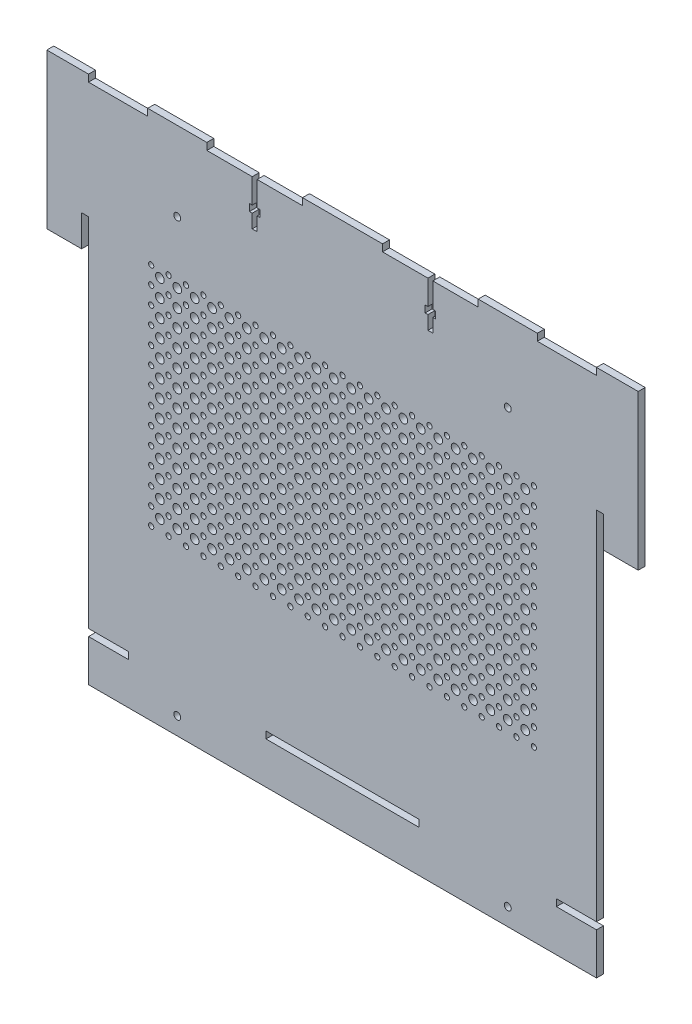
SolidWorks part; units mm, degrees
ref_plane "Front" through (0, 0, 0) normal (0, 0, 1) x (1, 0, 0)
ref_plane "Top" through (0, 0, 0) normal (0, 1, 0) x (1, 0, 0)
ref_plane "Right" through (0, 0, 0) normal (1, 0, 0) x (0, 0, -1)
sketch "Sketch1" plane through (0, 0, 0) normal (0, 0, 1) x (1, 0, 0)
  line L0 (-146, 106.5) -> (146, 106.5) construction
  line L1 (146, -152) -> (-146, -152)
  line L2 (146, -152) -> (146, -128)
  line L3 (146, 152) -> (-146, 152) construction
  line L4 (-146, -152) -> (-146, -128)
  line L5 (146, -152) -> (-146, 152) construction
  line L6 (146, 152) -> (-146, -152) construction
  line L7 (-146, 148) -> (-112, 148)
  line L8 (-112, 148) -> (-112, 152)
  line L9 (-112, 152) -> (-78, 152)
  line L10 (-78, 152) -> (-78, 148)
  line L11 (-78, 148) -> (-51.9, 148)
  line L12 (-23, 148) -> (-23, 152)
  line L13 (-23, 152) -> (23, 152)
  line L14 (23, 152) -> (23, 148)
  line L15 (23, 148) -> (49.1, 148)
  line L16 (78, 148) -> (78, 152)
  line L17 (78, 152) -> (112, 152)
  line L18 (112, 152) -> (112, 148)
  line L19 (112, 148) -> (146, 148)
  line L20 (-146, -142) -> (146, -142) construction
  line L21 (-95, 152) -> (-95, 106.5) construction
  line L22 (95, 152) -> (95, 106.5) construction
  line L23 (0, 106.5) -> (0, -142) construction
  line L24 (-146, 152) -> (-170, 152)
  line L25 (116.5, 80) -> (-116.5, 80) construction
  line L26 (116.5, 80) -> (116.5, -64) construction
  line L27 (116.5, -64) -> (-116.5, -64) construction
  line L28 (-116.5, 80) -> (-116.5, -64) construction
  line L29 (116.5, 80) -> (-116.5, -64) construction
  line L30 (116.5, -64) -> (-116.5, 80) construction
  line L31 (-170, 152) -> (-170, 63)
  line L32 (-170, 63) -> (-150, 63)
  line L33 (-150, 63) -> (-150, 81)
  line L34 (-150, 81) -> (-146, 81)
  line L35 (150, 81) -> (146, 81)
  line L36 (150, 63) -> (150, 81)
  line L37 (170, 63) -> (150, 63)
  line L38 (170, 152) -> (170, 63)
  line L39 (146, 152) -> (170, 152)
  line L40 (146, 148) -> (146, 152)
  line L41 (-146, 148) -> (-146, 152)
  line L42 (-50.5, 148) -> (-50.5, 122) construction
  line L43 (50.5, 148) -> (50.5, 122) construction
  line L44 (-51.9, 148) -> (-51.9, 133.8447)
  line L45 (49.1, 148) -> (49.1, 122)
  line L46 (-49.1, 148) -> (-49.1, 133.8447)
  line L47 (51.9, 148) -> (51.9, 122)
  line L48 (146, 122) -> (-146, 122) construction
  line L49 (-51.9, 122) -> (-49.1, 122)
  line L50 (-50.5, 148) -> (-50.5, 119.0546) construction
  line L51 (-51.9, 148) -> (-51.9, 119.0546) construction
  line L52 (49.1, 122) -> (51.9, 122)
  line L53 (50.5, 148) -> (50.5, 119.0546) construction
  line L54 (49.1, 148) -> (49.1, 119.0546) construction
  line L55 (-49.1, 148) -> (-23, 148)
  line L56 (51.9, 148) -> (78, 148)
  line L57 (-53.5, 133.8447) -> (-53.5, 129.8447)
  line L58 (-53.5, 133.8447) -> (-51.9, 133.8447)
  line L59 (-53.5, 129.8447) -> (-51.9, 129.8447)
  line L60 (-51.9, 129.8447) -> (-51.9, 122)
  line L61 (-47.5, 129.8447) -> (-49.1, 129.8447)
  line L62 (-47.5, 133.8447) -> (-47.5, 129.8447)
  line L63 (-47.5, 133.8447) -> (-49.1, 133.8447)
  line L64 (-49.1, 129.8447) -> (-49.1, 122)
  line L65 (-211.8235, -128) -> (236.7323, -128) construction
  line L66 (-146, -128) -> (-122.9474, -128)
  line L67 (-122.9474, -128) -> (-122.9474, -124)
  line L68 (-122.9474, -124) -> (-146, -124)
  line L69 (122.9474, -128) -> (146, -128)
  line L70 (122.9474, -128) -> (122.9474, -124)
  line L71 (122.9474, -124) -> (146, -124)
  line L72 (-44, -128) -> (-44, -124)
  line L73 (-44, -124) -> (44, -124)
  line L74 (44, -124) -> (44, -128)
  line L75 (-146, -124) -> (-146, 106.5)
  line L76 (146, -124) -> (146, 106.5)
  line L77 (-44, -128) -> (44, -128)
  line L78 (47.5, 133.8447) -> (49.1, 133.8447)
  line L79 (47.5, 133.8447) -> (47.5, 129.8447)
  line L80 (47.5, 129.8447) -> (49.1, 129.8447)
  line L81 (53.5, 129.8447) -> (51.9, 129.8447)
  line L82 (53.5, 133.8447) -> (51.9, 133.8447)
  line L83 (53.5, 133.8447) -> (53.5, 129.8447)
  circle A0 centre (-95, 106.5) radius 2
  circle A1 centre (95, 106.5) radius 2
  circle A2 centre (-95, -142) radius 2
  circle A3 centre (95, -142) radius 2
  circle A4 centre (-110, 75) radius 1.5
  circle A5 centre (-100, 75) radius 1.5
  circle A6 centre (-90, 75) radius 1.5
  circle A7 centre (-80, 75) radius 1.5
  circle A8 centre (-70, 75) radius 1.5
  circle A9 centre (-60, 75) radius 1.5
  circle A10 centre (-50, 75) radius 1.5
  circle A11 centre (-40, 75) radius 1.5
  circle A12 centre (-30, 75) radius 1.5
  circle A13 centre (-20, 75) radius 1.5
  circle A14 centre (-10, 75) radius 1.5
  circle A15 centre (0, 75) radius 1.5
  circle A16 centre (10, 75) radius 1.5
  circle A17 centre (20, 75) radius 1.5
  circle A18 centre (30, 75) radius 1.5
  circle A19 centre (40, 75) radius 1.5
  circle A20 centre (50, 75) radius 1.5
  circle A21 centre (60, 75) radius 1.5
  circle A22 centre (70, 75) radius 1.5
  circle A23 centre (80, 75) radius 1.5
  circle A24 centre (90, 75) radius 1.5
  circle A25 centre (100, 75) radius 1.5
  circle A26 centre (110, 75) radius 1.5
  circle A27 centre (-100, 65) radius 1.5
  circle A28 centre (-90, 65) radius 1.5
  circle A29 centre (-80, 65) radius 1.5
  circle A30 centre (-70, 65) radius 1.5
  circle A31 centre (-60, 65) radius 1.5
  circle A32 centre (-50, 65) radius 1.5
  circle A33 centre (-40, 65) radius 1.5
  circle A34 centre (-30, 65) radius 1.5
  circle A35 centre (-20, 65) radius 1.5
  circle A36 centre (-10, 65) radius 1.5
  circle A37 centre (0, 65) radius 1.5
  circle A38 centre (10, 65) radius 1.5
  circle A39 centre (20, 65) radius 1.5
  circle A40 centre (30, 65) radius 1.5
  circle A41 centre (40, 65) radius 1.5
  circle A42 centre (50, 65) radius 1.5
  circle A43 centre (60, 65) radius 1.5
  circle A44 centre (70, 65) radius 1.5
  circle A45 centre (80, 65) radius 1.5
  circle A46 centre (90, 65) radius 1.5
  circle A47 centre (100, 65) radius 1.5
  circle A48 centre (110, 65) radius 1.5
  circle A49 centre (-100, 55) radius 1.5
  circle A50 centre (-90, 55) radius 1.5
  circle A51 centre (-80, 55) radius 1.5
  circle A52 centre (-70, 55) radius 1.5
  circle A53 centre (-60, 55) radius 1.5
  circle A54 centre (-50, 55) radius 1.5
  circle A55 centre (-40, 55) radius 1.5
  circle A56 centre (-30, 55) radius 1.5
  circle A57 centre (-20, 55) radius 1.5
  circle A58 centre (-10, 55) radius 1.5
  circle A59 centre (0, 55) radius 1.5
  circle A60 centre (10, 55) radius 1.5
  circle A61 centre (20, 55) radius 1.5
  circle A62 centre (30, 55) radius 1.5
  circle A63 centre (40, 55) radius 1.5
  circle A64 centre (50, 55) radius 1.5
  circle A65 centre (60, 55) radius 1.5
  circle A66 centre (70, 55) radius 1.5
  circle A67 centre (80, 55) radius 1.5
  circle A68 centre (90, 55) radius 1.5
  circle A69 centre (100, 55) radius 1.5
  circle A70 centre (110, 55) radius 1.5
  circle A71 centre (-100, 45) radius 1.5
  circle A72 centre (-90, 45) radius 1.5
  circle A73 centre (-80, 45) radius 1.5
  circle A74 centre (-70, 45) radius 1.5
  circle A75 centre (-60, 45) radius 1.5
  circle A76 centre (-50, 45) radius 1.5
  circle A77 centre (-40, 45) radius 1.5
  circle A78 centre (-30, 45) radius 1.5
  circle A79 centre (-20, 45) radius 1.5
  circle A80 centre (-10, 45) radius 1.5
  circle A81 centre (0, 45) radius 1.5
  circle A82 centre (10, 45) radius 1.5
  circle A83 centre (20, 45) radius 1.5
  circle A84 centre (30, 45) radius 1.5
  circle A85 centre (40, 45) radius 1.5
  circle A86 centre (50, 45) radius 1.5
  circle A87 centre (60, 45) radius 1.5
  circle A88 centre (70, 45) radius 1.5
  circle A89 centre (80, 45) radius 1.5
  circle A90 centre (90, 45) radius 1.5
  circle A91 centre (100, 45) radius 1.5
  circle A92 centre (110, 45) radius 1.5
  circle A93 centre (-100, 35) radius 1.5
  circle A94 centre (-90, 35) radius 1.5
  circle A95 centre (-80, 35) radius 1.5
  circle A96 centre (-70, 35) radius 1.5
  circle A97 centre (-60, 35) radius 1.5
  circle A98 centre (-50, 35) radius 1.5
  circle A99 centre (-40, 35) radius 1.5
  circle A100 centre (-30, 35) radius 1.5
  circle A101 centre (-20, 35) radius 1.5
  circle A102 centre (-10, 35) radius 1.5
  circle A103 centre (0, 35) radius 1.5
  circle A104 centre (10, 35) radius 1.5
  circle A105 centre (20, 35) radius 1.5
  circle A106 centre (30, 35) radius 1.5
  circle A107 centre (40, 35) radius 1.5
  circle A108 centre (50, 35) radius 1.5
  circle A109 centre (60, 35) radius 1.5
  circle A110 centre (70, 35) radius 1.5
  circle A111 centre (80, 35) radius 1.5
  circle A112 centre (90, 35) radius 1.5
  circle A113 centre (100, 35) radius 1.5
  circle A114 centre (110, 35) radius 1.5
  circle A115 centre (-100, 25) radius 1.5
  circle A116 centre (-90, 25) radius 1.5
  circle A117 centre (-80, 25) radius 1.5
  circle A118 centre (-70, 25) radius 1.5
  circle A119 centre (-60, 25) radius 1.5
  circle A120 centre (-50, 25) radius 1.5
  circle A121 centre (-40, 25) radius 1.5
  circle A122 centre (-30, 25) radius 1.5
  circle A123 centre (-20, 25) radius 1.5
  circle A124 centre (-10, 25) radius 1.5
  circle A125 centre (0, 25) radius 1.5
  circle A126 centre (10, 25) radius 1.5
  circle A127 centre (20, 25) radius 1.5
  circle A128 centre (30, 25) radius 1.5
  circle A129 centre (40, 25) radius 1.5
  circle A130 centre (50, 25) radius 1.5
  circle A131 centre (60, 25) radius 1.5
  circle A132 centre (70, 25) radius 1.5
  circle A133 centre (80, 25) radius 1.5
  circle A134 centre (90, 25) radius 1.5
  circle A135 centre (100, 25) radius 1.5
  circle A136 centre (110, 25) radius 1.5
  circle A137 centre (-100, 15) radius 1.5
  circle A138 centre (-90, 15) radius 1.5
  circle A139 centre (-80, 15) radius 1.5
  circle A140 centre (-70, 15) radius 1.5
  circle A141 centre (-60, 15) radius 1.5
  circle A142 centre (-50, 15) radius 1.5
  circle A143 centre (-40, 15) radius 1.5
  circle A144 centre (-30, 15) radius 1.5
  circle A145 centre (-20, 15) radius 1.5
  circle A146 centre (-10, 15) radius 1.5
  circle A147 centre (0, 15) radius 1.5
  circle A148 centre (10, 15) radius 1.5
  circle A149 centre (20, 15) radius 1.5
  circle A150 centre (30, 15) radius 1.5
  circle A151 centre (40, 15) radius 1.5
  circle A152 centre (50, 15) radius 1.5
  circle A153 centre (60, 15) radius 1.5
  circle A154 centre (70, 15) radius 1.5
  circle A155 centre (80, 15) radius 1.5
  circle A156 centre (90, 15) radius 1.5
  circle A157 centre (100, 15) radius 1.5
  circle A158 centre (110, 15) radius 1.5
  circle A159 centre (-100, 5) radius 1.5
  circle A160 centre (-90, 5) radius 1.5
  circle A161 centre (-80, 5) radius 1.5
  circle A162 centre (-70, 5) radius 1.5
  circle A163 centre (-60, 5) radius 1.5
  circle A164 centre (-50, 5) radius 1.5
  circle A165 centre (-40, 5) radius 1.5
  circle A166 centre (-30, 5) radius 1.5
  circle A167 centre (-20, 5) radius 1.5
  circle A168 centre (-10, 5) radius 1.5
  circle A169 centre (0, 5) radius 1.5
  circle A170 centre (10, 5) radius 1.5
  circle A171 centre (20, 5) radius 1.5
  circle A172 centre (30, 5) radius 1.5
  circle A173 centre (40, 5) radius 1.5
  circle A174 centre (50, 5) radius 1.5
  circle A175 centre (60, 5) radius 1.5
  circle A176 centre (70, 5) radius 1.5
  circle A177 centre (80, 5) radius 1.5
  circle A178 centre (90, 5) radius 1.5
  circle A179 centre (100, 5) radius 1.5
  circle A180 centre (110, 5) radius 1.5
  circle A181 centre (-100, -5) radius 1.5
  circle A182 centre (-90, -5) radius 1.5
  circle A183 centre (-80, -5) radius 1.5
  circle A184 centre (-70, -5) radius 1.5
  circle A185 centre (-60, -5) radius 1.5
  circle A186 centre (-50, -5) radius 1.5
  circle A187 centre (-40, -5) radius 1.5
  circle A188 centre (-30, -5) radius 1.5
  circle A189 centre (-20, -5) radius 1.5
  circle A190 centre (-10, -5) radius 1.5
  circle A191 centre (0, -5) radius 1.5
  circle A192 centre (10, -5) radius 1.5
  circle A193 centre (20, -5) radius 1.5
  circle A194 centre (30, -5) radius 1.5
  circle A195 centre (40, -5) radius 1.5
  circle A196 centre (50, -5) radius 1.5
  circle A197 centre (60, -5) radius 1.5
  circle A198 centre (70, -5) radius 1.5
  circle A199 centre (80, -5) radius 1.5
  circle A200 centre (90, -5) radius 1.5
  circle A201 centre (100, -5) radius 1.5
  circle A202 centre (110, -5) radius 1.5
  circle A203 centre (-100, -15) radius 1.5
  circle A204 centre (-90, -15) radius 1.5
  circle A205 centre (-80, -15) radius 1.5
  circle A206 centre (-70, -15) radius 1.5
  circle A207 centre (-60, -15) radius 1.5
  circle A208 centre (-50, -15) radius 1.5
  circle A209 centre (-40, -15) radius 1.5
  circle A210 centre (-30, -15) radius 1.5
  circle A211 centre (-20, -15) radius 1.5
  circle A212 centre (-10, -15) radius 1.5
  circle A213 centre (0, -15) radius 1.5
  circle A214 centre (10, -15) radius 1.5
  circle A215 centre (20, -15) radius 1.5
  circle A216 centre (30, -15) radius 1.5
  circle A217 centre (40, -15) radius 1.5
  circle A218 centre (50, -15) radius 1.5
  circle A219 centre (60, -15) radius 1.5
  circle A220 centre (70, -15) radius 1.5
  circle A221 centre (80, -15) radius 1.5
  circle A222 centre (90, -15) radius 1.5
  circle A223 centre (100, -15) radius 1.5
  circle A224 centre (110, -15) radius 1.5
  circle A225 centre (-100, -25) radius 1.5
  circle A226 centre (-90, -25) radius 1.5
  circle A227 centre (-80, -25) radius 1.5
  circle A228 centre (-70, -25) radius 1.5
  circle A229 centre (-60, -25) radius 1.5
  circle A230 centre (-50, -25) radius 1.5
  circle A231 centre (-40, -25) radius 1.5
  circle A232 centre (-30, -25) radius 1.5
  circle A233 centre (-20, -25) radius 1.5
  circle A234 centre (-10, -25) radius 1.5
  circle A235 centre (0, -25) radius 1.5
  circle A236 centre (10, -25) radius 1.5
  circle A237 centre (20, -25) radius 1.5
  circle A238 centre (30, -25) radius 1.5
  circle A239 centre (40, -25) radius 1.5
  circle A240 centre (50, -25) radius 1.5
  circle A241 centre (60, -25) radius 1.5
  circle A242 centre (70, -25) radius 1.5
  circle A243 centre (80, -25) radius 1.5
  circle A244 centre (90, -25) radius 1.5
  circle A245 centre (100, -25) radius 1.5
  circle A246 centre (110, -25) radius 1.5
  circle A247 centre (-100, -35) radius 1.5
  circle A248 centre (-90, -35) radius 1.5
  circle A249 centre (-80, -35) radius 1.5
  circle A250 centre (-70, -35) radius 1.5
  circle A251 centre (-60, -35) radius 1.5
  circle A252 centre (-50, -35) radius 1.5
  circle A253 centre (-40, -35) radius 1.5
  circle A254 centre (-30, -35) radius 1.5
  circle A255 centre (-20, -35) radius 1.5
  circle A256 centre (-10, -35) radius 1.5
  circle A257 centre (0, -35) radius 1.5
  circle A258 centre (10, -35) radius 1.5
  circle A259 centre (20, -35) radius 1.5
  circle A260 centre (30, -35) radius 1.5
  circle A261 centre (40, -35) radius 1.5
  circle A262 centre (50, -35) radius 1.5
  circle A263 centre (60, -35) radius 1.5
  circle A264 centre (70, -35) radius 1.5
  circle A265 centre (80, -35) radius 1.5
  circle A266 centre (90, -35) radius 1.5
  circle A267 centre (100, -35) radius 1.5
  circle A268 centre (110, -35) radius 1.5
  circle A269 centre (-100, -45) radius 1.5
  circle A270 centre (-90, -45) radius 1.5
  circle A271 centre (-80, -45) radius 1.5
  circle A272 centre (-70, -45) radius 1.5
  circle A273 centre (-60, -45) radius 1.5
  circle A274 centre (-50, -45) radius 1.5
  circle A275 centre (-40, -45) radius 1.5
  circle A276 centre (-30, -45) radius 1.5
  circle A277 centre (-20, -45) radius 1.5
  circle A278 centre (-10, -45) radius 1.5
  circle A279 centre (0, -45) radius 1.5
  circle A280 centre (10, -45) radius 1.5
  circle A281 centre (20, -45) radius 1.5
  circle A282 centre (30, -45) radius 1.5
  circle A283 centre (40, -45) radius 1.5
  circle A284 centre (50, -45) radius 1.5
  circle A285 centre (60, -45) radius 1.5
  circle A286 centre (70, -45) radius 1.5
  circle A287 centre (80, -45) radius 1.5
  circle A288 centre (90, -45) radius 1.5
  circle A289 centre (100, -45) radius 1.5
  circle A290 centre (110, -45) radius 1.5
  circle A291 centre (-100, -55) radius 1.5
  circle A292 centre (-90, -55) radius 1.5
  circle A293 centre (-80, -55) radius 1.5
  circle A294 centre (-70, -55) radius 1.5
  circle A295 centre (-60, -55) radius 1.5
  circle A296 centre (-50, -55) radius 1.5
  circle A297 centre (-40, -55) radius 1.5
  circle A298 centre (-30, -55) radius 1.5
  circle A299 centre (-20, -55) radius 1.5
  circle A300 centre (-10, -55) radius 1.5
  circle A301 centre (0, -55) radius 1.5
  circle A302 centre (10, -55) radius 1.5
  circle A303 centre (20, -55) radius 1.5
  circle A304 centre (30, -55) radius 1.5
  circle A305 centre (40, -55) radius 1.5
  circle A306 centre (50, -55) radius 1.5
  circle A307 centre (60, -55) radius 1.5
  circle A308 centre (70, -55) radius 1.5
  circle A309 centre (80, -55) radius 1.5
  circle A310 centre (90, -55) radius 1.5
  circle A311 centre (100, -55) radius 1.5
  circle A312 centre (110, -55) radius 1.5
  circle A313 centre (-110, 65) radius 1.5
  circle A314 centre (-110, 55) radius 1.5
  circle A315 centre (-110, 45) radius 1.5
  circle A316 centre (-110, 35) radius 1.5
  circle A317 centre (-110, 25) radius 1.5
  circle A318 centre (-110, 15) radius 1.5
  circle A319 centre (-110, 5) radius 1.5
  circle A320 centre (-110, -5) radius 1.5
  circle A321 centre (-110, -15) radius 1.5
  circle A322 centre (-110, -25) radius 1.5
  circle A323 centre (-110, -35) radius 1.5
  circle A324 centre (-110, -45) radius 1.5
  circle A325 centre (-110, -55) radius 1.5
  circle A326 centre (-95, 71) radius 2.5
  circle A327 centre (-85, 71) radius 2.5
  circle A328 centre (-75, 71) radius 2.5
  circle A329 centre (-65, 71) radius 2.5
  circle A330 centre (-55, 71) radius 2.5
  circle A331 centre (-45, 71) radius 2.5
  circle A332 centre (-35, 71) radius 2.5
  circle A333 centre (-25, 71) radius 2.5
  circle A334 centre (-15, 71) radius 2.5
  circle A335 centre (-5, 71) radius 2.5
  circle A336 centre (5, 71) radius 2.5
  circle A337 centre (15, 71) radius 2.5
  circle A338 centre (25, 71) radius 2.5
  circle A339 centre (35, 71) radius 2.5
  circle A340 centre (45, 71) radius 2.5
  circle A341 centre (55, 71) radius 2.5
  circle A342 centre (65, 71) radius 2.5
  circle A343 centre (75, 71) radius 2.5
  circle A344 centre (85, 71) radius 2.5
  circle A345 centre (95, 71) radius 2.5
  circle A346 centre (105, 71) radius 2.5
  circle A347 centre (-95, 61) radius 2.5
  circle A348 centre (-85, 61) radius 2.5
  circle A349 centre (-75, 61) radius 2.5
  circle A350 centre (-65, 61) radius 2.5
  circle A351 centre (-55, 61) radius 2.5
  circle A352 centre (-45, 61) radius 2.5
  circle A353 centre (-35, 61) radius 2.5
  circle A354 centre (-25, 61) radius 2.5
  circle A355 centre (-15, 61) radius 2.5
  circle A356 centre (-5, 61) radius 2.5
  circle A357 centre (5, 61) radius 2.5
  circle A358 centre (15, 61) radius 2.5
  circle A359 centre (25, 61) radius 2.5
  circle A360 centre (35, 61) radius 2.5
  circle A361 centre (45, 61) radius 2.5
  circle A362 centre (55, 61) radius 2.5
  circle A363 centre (65, 61) radius 2.5
  circle A364 centre (75, 61) radius 2.5
  circle A365 centre (85, 61) radius 2.5
  circle A366 centre (95, 61) radius 2.5
  circle A367 centre (105, 61) radius 2.5
  circle A368 centre (-95, 51) radius 2.5
  circle A369 centre (-85, 51) radius 2.5
  circle A370 centre (-75, 51) radius 2.5
  circle A371 centre (-65, 51) radius 2.5
  circle A372 centre (-55, 51) radius 2.5
  circle A373 centre (-45, 51) radius 2.5
  circle A374 centre (-35, 51) radius 2.5
  circle A375 centre (-25, 51) radius 2.5
  circle A376 centre (-15, 51) radius 2.5
  circle A377 centre (-5, 51) radius 2.5
  circle A378 centre (5, 51) radius 2.5
  circle A379 centre (15, 51) radius 2.5
  circle A380 centre (25, 51) radius 2.5
  circle A381 centre (35, 51) radius 2.5
  circle A382 centre (45, 51) radius 2.5
  circle A383 centre (55, 51) radius 2.5
  circle A384 centre (65, 51) radius 2.5
  circle A385 centre (75, 51) radius 2.5
  circle A386 centre (85, 51) radius 2.5
  circle A387 centre (95, 51) radius 2.5
  circle A388 centre (105, 51) radius 2.5
  circle A389 centre (-95, 41) radius 2.5
  circle A390 centre (-85, 41) radius 2.5
  circle A391 centre (-75, 41) radius 2.5
  circle A392 centre (-65, 41) radius 2.5
  circle A393 centre (-55, 41) radius 2.5
  circle A394 centre (-45, 41) radius 2.5
  circle A395 centre (-35, 41) radius 2.5
  circle A396 centre (-25, 41) radius 2.5
  circle A397 centre (-15, 41) radius 2.5
  circle A398 centre (-5, 41) radius 2.5
  circle A399 centre (5, 41) radius 2.5
  circle A400 centre (15, 41) radius 2.5
  circle A401 centre (25, 41) radius 2.5
  circle A402 centre (35, 41) radius 2.5
  circle A403 centre (45, 41) radius 2.5
  circle A404 centre (55, 41) radius 2.5
  circle A405 centre (65, 41) radius 2.5
  circle A406 centre (75, 41) radius 2.5
  circle A407 centre (85, 41) radius 2.5
  circle A408 centre (95, 41) radius 2.5
  circle A409 centre (105, 41) radius 2.5
  circle A410 centre (-95, 31) radius 2.5
  circle A411 centre (-85, 31) radius 2.5
  circle A412 centre (-75, 31) radius 2.5
  circle A413 centre (-65, 31) radius 2.5
  circle A414 centre (-55, 31) radius 2.5
  circle A415 centre (-45, 31) radius 2.5
  circle A416 centre (-35, 31) radius 2.5
  circle A417 centre (-25, 31) radius 2.5
  circle A418 centre (-105, 71) radius 2.5
  circle A419 centre (-15, 31) radius 2.5
  circle A420 centre (-5, 31) radius 2.5
  circle A421 centre (5, 31) radius 2.5
  circle A422 centre (15, 31) radius 2.5
  circle A423 centre (25, 31) radius 2.5
  circle A424 centre (35, 31) radius 2.5
  circle A425 centre (45, 31) radius 2.5
  circle A426 centre (55, 31) radius 2.5
  circle A427 centre (65, 31) radius 2.5
  circle A428 centre (75, 31) radius 2.5
  circle A429 centre (85, 31) radius 2.5
  circle A430 centre (95, 31) radius 2.5
  circle A431 centre (105, 31) radius 2.5
  circle A432 centre (-95, 21) radius 2.5
  circle A433 centre (-85, 21) radius 2.5
  circle A434 centre (-75, 21) radius 2.5
  circle A435 centre (-65, 21) radius 2.5
  circle A436 centre (-55, 21) radius 2.5
  circle A437 centre (-45, 21) radius 2.5
  circle A438 centre (-35, 21) radius 2.5
  circle A439 centre (-25, 21) radius 2.5
  circle A440 centre (-15, 21) radius 2.5
  circle A441 centre (-5, 21) radius 2.5
  circle A442 centre (5, 21) radius 2.5
  circle A443 centre (15, 21) radius 2.5
  circle A444 centre (25, 21) radius 2.5
  circle A445 centre (35, 21) radius 2.5
  circle A446 centre (45, 21) radius 2.5
  circle A447 centre (55, 21) radius 2.5
  circle A448 centre (65, 21) radius 2.5
  circle A449 centre (75, 21) radius 2.5
  circle A450 centre (85, 21) radius 2.5
  circle A451 centre (95, 21) radius 2.5
  circle A452 centre (105, 21) radius 2.5
  circle A453 centre (-95, 11) radius 2.5
  circle A454 centre (-85, 11) radius 2.5
  circle A455 centre (-75, 11) radius 2.5
  circle A456 centre (-65, 11) radius 2.5
  circle A457 centre (-55, 11) radius 2.5
  circle A458 centre (-45, 11) radius 2.5
  circle A459 centre (-35, 11) radius 2.5
  circle A460 centre (-25, 11) radius 2.5
  circle A461 centre (-15, 11) radius 2.5
  circle A462 centre (-5, 11) radius 2.5
  circle A463 centre (5, 11) radius 2.5
  circle A464 centre (15, 11) radius 2.5
  circle A465 centre (25, 11) radius 2.5
  circle A466 centre (35, 11) radius 2.5
  circle A467 centre (45, 11) radius 2.5
  circle A468 centre (55, 11) radius 2.5
  circle A469 centre (65, 11) radius 2.5
  circle A470 centre (75, 11) radius 2.5
  circle A471 centre (85, 11) radius 2.5
  circle A472 centre (95, 11) radius 2.5
  circle A473 centre (105, 11) radius 2.5
  circle A474 centre (-95, 1) radius 2.5
  circle A475 centre (-85, 1) radius 2.5
  circle A476 centre (-75, 1) radius 2.5
  circle A477 centre (-65, 1) radius 2.5
  circle A478 centre (-55, 1) radius 2.5
  circle A479 centre (-45, 1) radius 2.5
  circle A480 centre (-35, 1) radius 2.5
  circle A481 centre (-25, 1) radius 2.5
  circle A482 centre (-15, 1) radius 2.5
  circle A483 centre (-5, 1) radius 2.5
  circle A484 centre (5, 1) radius 2.5
  circle A485 centre (15, 1) radius 2.5
  circle A486 centre (25, 1) radius 2.5
  circle A487 centre (35, 1) radius 2.5
  circle A488 centre (45, 1) radius 2.5
  circle A489 centre (55, 1) radius 2.5
  circle A490 centre (65, 1) radius 2.5
  circle A491 centre (75, 1) radius 2.5
  circle A492 centre (85, 1) radius 2.5
  circle A493 centre (95, 1) radius 2.5
  circle A494 centre (105, 1) radius 2.5
  circle A495 centre (-95, -9) radius 2.5
  circle A496 centre (-85, -9) radius 2.5
  circle A497 centre (-75, -9) radius 2.5
  circle A498 centre (-65, -9) radius 2.5
  circle A499 centre (-55, -9) radius 2.5
  circle A500 centre (-45, -9) radius 2.5
  circle A501 centre (-35, -9) radius 2.5
  circle A502 centre (-25, -9) radius 2.5
  circle A503 centre (-15, -9) radius 2.5
  circle A504 centre (-5, -9) radius 2.5
  circle A505 centre (5, -9) radius 2.5
  circle A506 centre (15, -9) radius 2.5
  circle A507 centre (25, -9) radius 2.5
  circle A508 centre (35, -9) radius 2.5
  circle A509 centre (45, -9) radius 2.5
  circle A510 centre (55, -9) radius 2.5
  circle A511 centre (65, -9) radius 2.5
  circle A512 centre (75, -9) radius 2.5
  circle A513 centre (85, -9) radius 2.5
  circle A514 centre (95, -9) radius 2.5
  circle A515 centre (105, -9) radius 2.5
  circle A516 centre (-95, -19) radius 2.5
  circle A517 centre (-85, -19) radius 2.5
  circle A518 centre (-75, -19) radius 2.5
  circle A519 centre (-65, -19) radius 2.5
  circle A520 centre (-55, -19) radius 2.5
  circle A521 centre (-45, -19) radius 2.5
  circle A522 centre (-35, -19) radius 2.5
  circle A523 centre (-25, -19) radius 2.5
  circle A524 centre (-15, -19) radius 2.5
  circle A525 centre (-5, -19) radius 2.5
  circle A526 centre (5, -19) radius 2.5
  circle A527 centre (15, -19) radius 2.5
  circle A528 centre (25, -19) radius 2.5
  circle A529 centre (35, -19) radius 2.5
  circle A530 centre (45, -19) radius 2.5
  circle A531 centre (55, -19) radius 2.5
  circle A532 centre (65, -19) radius 2.5
  circle A533 centre (75, -19) radius 2.5
  circle A534 centre (85, -19) radius 2.5
  circle A535 centre (95, -19) radius 2.5
  circle A536 centre (105, -19) radius 2.5
  circle A537 centre (-95, -29) radius 2.5
  circle A538 centre (-85, -29) radius 2.5
  circle A539 centre (-75, -29) radius 2.5
  circle A540 centre (-65, -29) radius 2.5
  circle A541 centre (-55, -29) radius 2.5
  circle A542 centre (-45, -29) radius 2.5
  circle A543 centre (-35, -29) radius 2.5
  circle A544 centre (-25, -29) radius 2.5
  circle A545 centre (-15, -29) radius 2.5
  circle A546 centre (-5, -29) radius 2.5
  circle A547 centre (5, -29) radius 2.5
  circle A548 centre (15, -29) radius 2.5
  circle A549 centre (25, -29) radius 2.5
  circle A550 centre (35, -29) radius 2.5
  circle A551 centre (45, -29) radius 2.5
  circle A552 centre (55, -29) radius 2.5
  circle A553 centre (65, -29) radius 2.5
  circle A554 centre (75, -29) radius 2.5
  circle A555 centre (85, -29) radius 2.5
  circle A556 centre (95, -29) radius 2.5
  circle A557 centre (105, -29) radius 2.5
  circle A558 centre (-95, -39) radius 2.5
  circle A559 centre (-85, -39) radius 2.5
  circle A560 centre (-75, -39) radius 2.5
  circle A561 centre (-65, -39) radius 2.5
  circle A562 centre (-55, -39) radius 2.5
  circle A563 centre (-45, -39) radius 2.5
  circle A564 centre (-35, -39) radius 2.5
  circle A565 centre (-25, -39) radius 2.5
  circle A566 centre (-15, -39) radius 2.5
  circle A567 centre (-5, -39) radius 2.5
  circle A568 centre (5, -39) radius 2.5
  circle A569 centre (15, -39) radius 2.5
  circle A570 centre (25, -39) radius 2.5
  circle A571 centre (35, -39) radius 2.5
  circle A572 centre (45, -39) radius 2.5
  circle A573 centre (55, -39) radius 2.5
  circle A574 centre (65, -39) radius 2.5
  circle A575 centre (75, -39) radius 2.5
  circle A576 centre (85, -39) radius 2.5
  circle A577 centre (95, -39) radius 2.5
  circle A578 centre (105, -39) radius 2.5
  circle A579 centre (-95, -49) radius 2.5
  circle A580 centre (-85, -49) radius 2.5
  circle A581 centre (-75, -49) radius 2.5
  circle A582 centre (-65, -49) radius 2.5
  circle A583 centre (-55, -49) radius 2.5
  circle A584 centre (-45, -49) radius 2.5
  circle A585 centre (-35, -49) radius 2.5
  circle A586 centre (-25, -49) radius 2.5
  circle A587 centre (-15, -49) radius 2.5
  circle A588 centre (-5, -49) radius 2.5
  circle A589 centre (5, -49) radius 2.5
  circle A590 centre (15, -49) radius 2.5
  circle A591 centre (25, -49) radius 2.5
  circle A592 centre (35, -49) radius 2.5
  circle A593 centre (45, -49) radius 2.5
  circle A594 centre (55, -49) radius 2.5
  circle A595 centre (65, -49) radius 2.5
  circle A596 centre (75, -49) radius 2.5
  circle A597 centre (85, -49) radius 2.5
  circle A598 centre (95, -49) radius 2.5
  circle A599 centre (105, -49) radius 2.5
  circle A600 centre (-105, 61) radius 2.5
  circle A601 centre (-105, 51) radius 2.5
  circle A602 centre (-105, 41) radius 2.5
  circle A603 centre (-105, 31) radius 2.5
  circle A604 centre (-105, 21) radius 2.5
  circle A605 centre (-105, 11) radius 2.5
  circle A606 centre (-105, 1) radius 2.5
  circle A607 centre (-105, -9) radius 2.5
  circle A608 centre (-105, -19) radius 2.5
  circle A609 centre (-105, -29) radius 2.5
  circle A610 centre (-105, -39) radius 2.5
  circle A611 centre (-105, -49) radius 2.5
  point P0 (0, 8)
  dimension "D12" = 4
  dimension "D13" = 8
  dimension "D14" = 4
  dimension "D15" = 4
  dimension "D19" = 3
  dimension "D24" = 5
  dimension "D1" = 304
  dimension "D2" = 292
  dimension "D3" = 4
  dimension "D4" = 34
  dimension "D5" = 34
  dimension "D6" = 34
  dimension "D7" = 34
  dimension "D8" = 55
  dimension "D9" = 55
  dimension "D10" = 41.5
  dimension "D11" = 10
  dimension "D16" = 9
  dimension "D17" = 233
  dimension "D18" = 144
  dimension "D20" = 6.5
  dimension "D21" = 5
  dimension "D25" = 44
  dimension "D27" = 11.5
  dimension "D28" = 4
  dimension "D29" = 71
  dimension "D30" = 24
  dimension "D31" = 89
  dimension "D35" = 27.5
  dimension "D36" = 27.5
  dimension "D37" = 4
  dimension "D38" = 3
  dimension "D22" = 24
  dimension "D23" = 4
  dimension "D26" = 44
  dimension "D32" = 1.4
  dimension "D34" = 30
extrude "Boss-Extrude1" add sketch "Sketch1" along normal blind 4 contours L19 L18 L17 L16 L15 L14 L13 L12 L11 L10 L9 L8 L7 L4 L1 L2 A3 A2 A1 A0 region at (0, -147.4391, 0)
